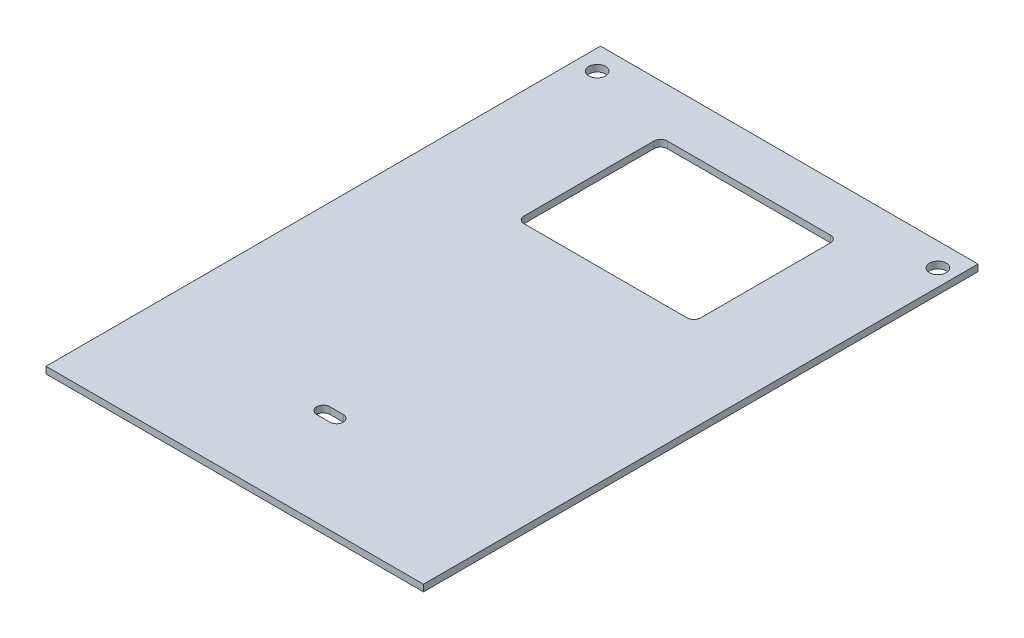
SolidWorks part; units mm, degrees
ref_plane "Plan de face" through (0, 0, 0) normal (0, 0, 1) x (1, 0, 0)
ref_plane "Plan de dessus" through (0, 0, 0) normal (0, 1, 0) x (1, 0, 0)
ref_plane "Plan de droite" through (0, 0, 0) normal (1, 0, 0) x (0, 0, -1)
sketch "Sketch1" plane through (0, 0, 0) normal (0, 1, 0) x (1, 0, 0)
  line L1 (-56.5, 83) -> (56.5, 83)
  line L2 (-56.5, 83) -> (-56.5, -83)
  line L3 (-56.5, -83) -> (56.5, -83)
  line L4 (56.5, 83) -> (56.5, -83)
  line L5 (-56.5, 83) -> (56.5, -83) construction
  line L6 (-56.5, -83) -> (56.5, 83) construction
  point P0 (0, 0)
  dimension "D1" = 113
  dimension "D2" = 166
extrude "Boss-Extrude1" add sketch "Sketch1" along normal blind 2
sketch "Sketch2" plane through (0, 2, 0) normal (0, 1, 0) x (1, 0, 0)
  line L0 (56.5, -83) -> (56.5, 83) construction
  line L1 (56.5, 83) -> (-56.5, 83) construction
  line L2 (-56.5, 83) -> (-56.5, -83) construction
  line L3 (-56.5, -83) -> (56.5, -83) construction
  line L4 (-5.5, -51) -> (2.5, -51)
  line L5 (-5.5, -51) -> (-5.5, -55)
  line L6 (-5.5, -55) -> (2.5, -55)
  line L7 (2.5, -51) -> (2.5, -55)
  line L8 (-5.5, -51) -> (2.5, -55) construction
  line L9 (-5.5, -55) -> (2.5, -51) construction
  circle A0 centre (51.5, 76) radius 2.5
  circle A1 centre (-50.5, 76) radius 2.5
  point P10 (-1.5, -53)
  dimension "D3" = 5
  dimension "D4" = 5
  dimension "D1" = 5
  dimension "D2" = 7
  dimension "D5" = 6
  dimension "D6" = 7
  dimension "D7" = 30
  dimension "D8" = 55
  dimension "D9" = 4
  dimension "D10" = 8
extrude "Cut-Extrude1" cut sketch "Sketch2" against normal up to next
fillet "Fillet1" radius 2 4 edges at (-5.5, 1, 55) (-5.5, 1, 51) (2.5, 1, 55) (2.5, 1, 51)
sketch "Sketch3" plane through (0, 0, 0) normal (0, -1, 0) x (1, 0, 0)
  line L0 (56.5, 83) -> (56.5, -83) construction
  line L1 (-28.5, 15.5797) -> (11.5, 15.5797)
  line L2 (-28.5, 15.5797) -> (-28.5, 10.5797)
  line L3 (-28.5, 10.5797) -> (11.5, 10.5797)
  line L4 (11.5, 15.5797) -> (11.5, 10.5797)
  line L5 (-28.5, 15.5797) -> (11.5, 10.5797) construction
  line L6 (-28.5, 10.5797) -> (11.5, 15.5797) construction
  point P0 (-8.5, 13.0797)
  dimension "D1" = 65
  dimension "D2" = 40
  dimension "D3" = 5
extrude "Boss-Extrude2" add sketch "Sketch3" along normal blind 10
sketch "Sketch5" plane through (0, 0, 15.5797) normal (0, 0, 1) x (1, 0, 0)
  line L0 (-28.5, -5) -> (11.5, -5) construction
  line L1 (-28.5, -10) -> (-28.5, 0) construction
  line L2 (11.5, -10) -> (11.5, 0) construction
  line L3 (11.5, -5) -> (-8.5, -5) construction
  line L4 (-8.5, -5) -> (-8.5389, -19) construction
  line L5 (-8.5389, -7.6318) -> (-8.5389, -15.3318) construction
  line L6 (-56.5, 0) -> (56.5, 0) construction
  circle A0 centre (-8.5389, -19) radius 19
  dimension "D1" = 19
extrude "Cut-Extrude2" cut sketch "Sketch5" against normal up to next contours A0
sketch "Sketch6" plane through (0, 0, 15.5797) normal (0, 0, 1) x (1, 0, 0)
  line L0 (-56.5, 0) -> (56.5, 0) construction
  line L1 (11.5, -10) -> (11.5, 0) construction
  circle A0 centre (7.5, -4) radius 2
  dimension "D3" = 4
  dimension "D1" = 4
  dimension "D2" = 4
extrude "Cut-Extrude3" cut sketch "Sketch6" against normal up to next
ref_plane "Plane1" through (-8.5, 0, 0) normal (1, 0, 0) x (0, 0, -1)
mirror "Mirror1" about plane through (-8.5, 0, 0) normal (1, 0, 0) of "Cut-Extrude3"
sketch "Sketch7" plane through (0, 2, 0) normal (0, 1, 0) x (1, 0, 0)
  line L1 (28.9366, 68.4141) -> (-23.9083, 68.4141)
  line L2 (28.9366, 68.4141) -> (28.9366, 25.5)
  line L3 (28.9366, 25.5) -> (-23.9083, 25.5)
  line L4 (-23.9083, 68.4141) -> (-23.9083, 25.5)
extrude "Cut-Extrude4" cut sketch "Sketch7" against normal up to next
fillet "Fillet2" radius 2 4 edges at (28.9366, 1, -25.5) (28.9366, 1, -68.4141) (-23.9083, 1, -68.4141) (-23.9083, 1, -25.5)
